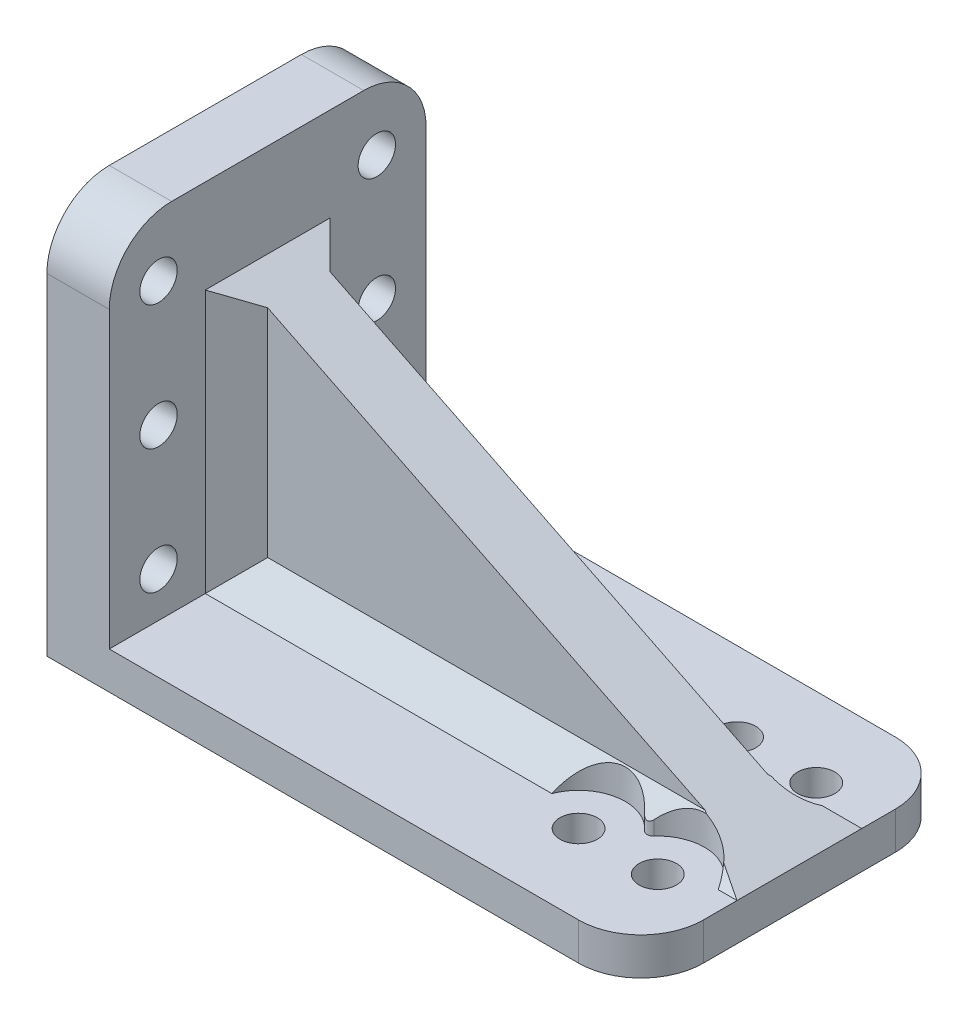
SolidWorks part; units mm, degrees
ref_plane "Front Plane" through (0, 0, 0) normal (0, 0, 1) x (1, 0, 0)
ref_plane "Top Plane" through (0, 0, 0) normal (0, 1, 0) x (1, 0, 0)
ref_plane "Right Plane" through (0, 0, 0) normal (1, 0, 0) x (0, 0, -1)
sketch "Sketch1" plane through (0, 0, 0) normal (0, 0, 1) x (1, 0, 0)
  line L1 (-47.625, 3) -> (47.625, 3)
  line L2 (-47.625, 3) -> (-47.625, -3)
  line L3 (-47.625, -3) -> (47.625, -3)
  line L4 (47.625, 3) -> (47.625, -3)
  line L5 (-47.625, 3) -> (47.625, -3) construction
  line L6 (-47.625, -3) -> (47.625, 3) construction
  line L7 (-47.625, 3) -> (-37.625, 3)
  line L8 (-47.625, 3) -> (-47.625, 60.15)
  line L9 (-47.625, 60.15) -> (-37.625, 60.15)
  line L10 (-37.625, 3) -> (-37.625, 60.15)
  point P0 (0, 0)
  dimension "D2" = 57.15
  dimension "D3" = 95.25
  dimension "D1" = 10
  dimension "D4" = 6
extrude "Boss-Extrude1" add sketch "Sketch1" along normal mid plane 50.8 contours L1 L10 L9 L8 | L4 L1 L2 L3
sketch "Sketch2" plane through (0, 0, 0) normal (0, 0, 1) x (1, 0, 0)
  line L0 (-37.625, 45.15) -> (47.625, 3)
  line L1 (-37.625, 3) -> (-37.625, 60.15) construction
  dimension "D1" = 15
rib "Rib1" sketch "Sketch2" sketch "Sketch2" thickness 10 extrusion direction parallel to sketch draft on no parameters "D1"=10
chamfer "Chamfer2" distance 5 angle 45 2 edges at (5, 3, 5) (-37.625, 24.075, 5)
chamfer "Chamfer3" distance 5 angle 45 2 edges at (-37.625, 24.075, -5) (5, 3, -5)
sketch "Sketch3" plane through (0, 3, 0) normal (0, 1, 0) x (1, 0, 0)
  line L0 (24.925, 12.7) -> (37.625, 12.7) construction
  line L1 (37.625, 12.7) -> (37.625, -12.7) construction
  line L2 (37.625, -12.7) -> (24.925, -12.7) construction
  line L3 (24.925, -12.7) -> (24.925, 12.7) construction
  line L4 (37.625, 0) -> (0, 0) construction
  line L5 (47.625, 10) -> (47.625, 25.4) construction
  circle A0 centre (24.925, 12.7) radius 3
  circle A1 centre (24.925, -12.7) radius 3
  circle A2 centre (37.625, -12.7) radius 3
  circle A3 centre (37.625, 12.7) radius 3
  dimension "D3" = 6
  dimension "D1" = 12.7
  dimension "D2" = 10
  dimension "D4" = 25.4
extrude "Cut-Extrude1" cut sketch "Sketch3" against normal through all both and the other way through all
sketch "Sketch4" plane through (0, 3, 0) normal (0, 1, 0) x (1, 0, 0)
  circle A0 centre (24.925, 12.7) radius 7.5
  circle A1 centre (37.625, 12.7) radius 7.5
  circle A2 centre (37.625, -12.7) radius 7.5
  circle A3 centre (24.925, -12.7) radius 7.5
  arc M5 (38.9327, -10) -> (36.3173, -10) centre (37.625, -12.7) cw
  line M6 (36.3173, -10) -> (26.2327, -10)
  arc M7 (26.2327, -10) -> (23.6173, -10) centre (24.925, -12.7) cw
  line M8 (23.6173, -10) -> (-37.625, -10)
  line M12 (47.625, -10) -> (38.9327, -10)
  dimension "D1" = 15
extrude "Cut-Extrude2" cut sketch "Sketch4" along normal through all contours A3 A2 M6 M5 M12 | A2 A3 M8 M7 M6 | A3 A2 M6 | A0 A1 | A0 A1 | A1 A0
fillet "Fillet1" radius 10 2 edges at (47.625, 0, -25.4) (47.625, 0, 25.4)
fillet "Fillet2" radius 10 2 edges at (-42.625, 60.15, -25.4) (-42.625, 60.15, 25.4)
sketch "Sketch5" plane through (-37.625, 0, 0) normal (1, 0, 0) x (0, 0, -1)
  line L0 (-17.5, 50.15) -> (17.5, 50.15) construction
  line L1 (17.5, 50.15) -> (17.5, 10.15) construction
  line L2 (17.5, 10.15) -> (-17.5, 10.15) construction
  line L3 (-17.5, 10.15) -> (-17.5, 50.15) construction
  line L4 (0, 50.15) -> (0, 0) construction
  line L6 (-15.4, 60.15) -> (15.4, 60.15) construction
  line L7 (-17.5, 30.15) -> (17.5, 30.15) construction
  circle A0 centre (-17.5, 50.15) radius 3
  circle A1 centre (17.5, 50.15) radius 3
  circle A2 centre (17.5, 30.15) radius 3
  circle A3 centre (-17.5, 30.15) radius 3
  circle A4 centre (-17.5, 10.15) radius 3
  circle A5 centre (17.5, 10.15) radius 3
  dimension "D4" = 6
  dimension "D1" = 35
  dimension "D2" = 40
  dimension "D3" = 10
extrude "Cut-Extrude3" cut sketch "Sketch5" against normal up to next
fillet "Fillet3" radius 1 2 edges at (31.275, 3.6455, -8.7091) (31.275, 3.6455, 8.7091)
equation "\"Length\" = 3.75in"
equation "\"Height\"= 2.25in"
equation "\"Thick\"= 10"
equation "\"D2@Sketch1\"=\"Height\""
equation "\"D3@Sketch1\"=\"Length\""
equation "\"D1@Sketch1\"=\"Thick\""
